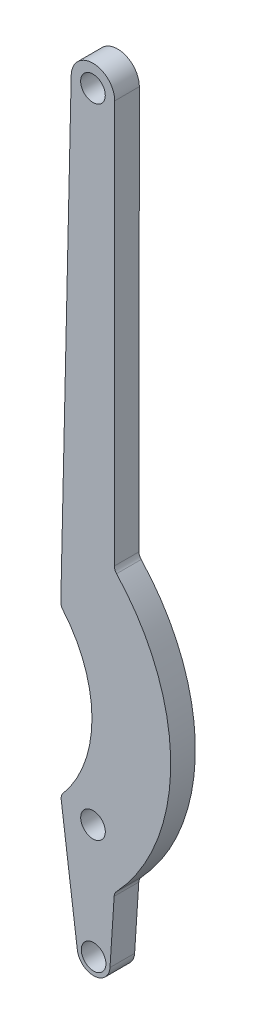
SolidWorks part; units mm, degrees
material "7075-O (SS)"
ref_plane "前视基准面" through (0, 0, 0) normal (0, 0, 1) x (1, 0, 0)
ref_plane "上视基准面" through (0, 0, 0) normal (0, 1, 0) x (1, 0, 0)
ref_plane "右视基准面" through (0, 0, 0) normal (1, 0, 0) x (0, 0, -1)
sketch "草图1" plane through (0, 0, 0) normal (0, 0, 1) x (1, 0, 0)
  line L0 (-1.9828, -0.2616) -> (-3.945, 14.6095)
  line L1 (1.9958, -0.1301) -> (2.502, 7.6348)
  line L2 (-4.0038, 15.055) -> (-4.0038, 35.0224) construction
  line L3 (-4.0038, 25.0387) -> (-15.1987, 25.0387) construction
  line L4 (2.5258, 42.4807) -> (2.5703, 91.5583)
  line L5 (-3.9951, 35.4091) -> (-2.7278, 91.6205)
  line L6 (-3.9135, 15.0205) -> (-0.0738, 13.8996) construction
  circle A0 centre (0, 0) radius 1.5
  arc A1 (-1.9828, -0.2616) -> (1.9958, -0.1301) centre (0, 0) ccw
  arc A4 (-3.7189, 15.3839) -> (-3.758, 34.7398) centre (-15.1987, 25.0387) ccw
  arc A5 (2.7691, 8.2525) -> (2.7941, 41.7982) centre (-15.1987, 25.0387) ccw
  arc A8 (2.5703, 91.5583) -> (-2.7278, 91.6205) centre (-0.0791, 91.5607) ccw
  circle A9 centre (-0.0791, 91.5607) radius 1.5
  arc A10 (-3.7189, 15.3839) -> (-3.945, 14.6095) centre (-2.9536, 14.7403) ccw
  arc A11 (2.7691, 8.2525) -> (2.502, 7.6348) centre (3.4998, 7.5698) ccw
  arc A12 (2.5258, 42.4807) -> (2.7941, 41.7982) centre (3.5258, 42.4798) ccw
  arc A13 (-3.9951, 35.4091) -> (-3.758, 34.7398) centre (-2.9953, 35.3865) ccw
  circle A15 centre (-0.0738, 13.8996) radius 1.5
  point P20 (2.5255, 7.9954)
  point P23 (2.5255, 42.082)
  dimension "D1" = 1
extrude "凸台-拉伸1" add sketch "草图1" along normal blind 3
